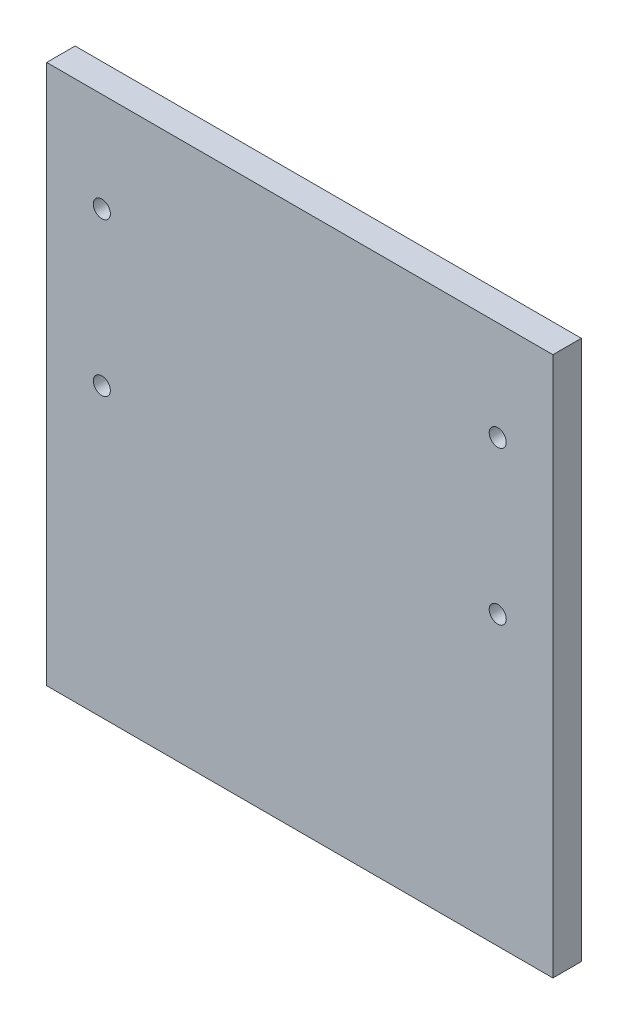
SolidWorks part; units mm, degrees
ref_plane "Front Plane" through (0, 0, 0) normal (0, 0, 1) x (1, 0, 0)
ref_plane "Top Plane" through (0, 0, 0) normal (0, 1, 0) x (1, 0, 0)
ref_plane "Right Plane" through (0, 0, 0) normal (1, 0, 0) x (0, 0, -1)
sketch "Sketch1" plane through (0, 0, 0) normal (0, 0, 1) x (1, 0, 0)
  line L1 (-44.5, -47.45) -> (44.5, -47.45)
  line L2 (-44.5, -47.45) -> (-44.5, 47.45)
  line L3 (-44.5, 47.45) -> (44.5, 47.45)
  line L4 (44.5, -47.45) -> (44.5, 47.45)
  line L5 (-44.5, -47.45) -> (44.5, 47.45) construction
  line L6 (-44.5, 47.45) -> (44.5, -47.45) construction
  point P0 (0, 0)
  dimension "D1" = 89
  dimension "D2" = 94.9
extrude "Boss-Extrude1" add sketch "Sketch1" along normal blind 5
sketch "Sketch2" plane through (0, 0, 5) normal (0, 0, 1) x (1, 0, 0)
  circle A0 centre (-34.8, 30) radius 1.5
  circle A1 centre (34.8, 30) radius 1.5
  circle A2 centre (34.8, 3.08) radius 1.5
  circle A3 centre (-34.8, 3.08) radius 1.5
  dimension "D1" = 3
  dimension "D5" = 2
  dimension "D2" = 30
  dimension "D4" = 34.8
  dimension "D3" = 2
extrude "Cut-Extrude1" cut sketch "Sketch2" against normal blind 5
